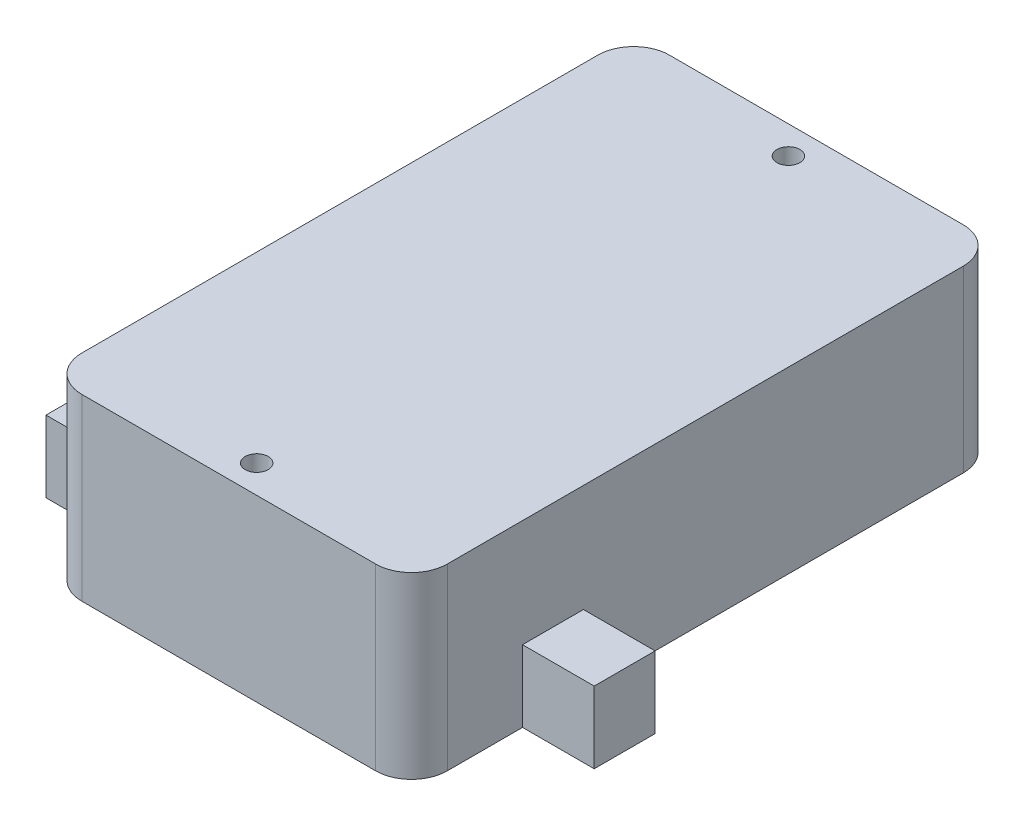
SolidWorks part; units mm, degrees
ref_plane "Front Plane" through (0, 0, 0) normal (0, 0, 1) x (1, 0, 0)
ref_plane "Top Plane" through (0, 0, 0) normal (0, 1, 0) x (1, 0, 0)
ref_plane "Right Plane" through (0, 0, 0) normal (1, 0, 0) x (0, 0, -1)
sketch "Sketch1" plane through (0, 0, 0) normal (0, 1, 0) x (1, 0, 0)
  line L0 (-25.5, 0) -> (25.5, 0) construction
  line L1 (-25.5, -41) -> (25.5, -41)
  line L2 (-25.5, -41) -> (-25.5, 41)
  line L3 (-25.5, 41) -> (25.5, 41)
  line L4 (25.5, -41) -> (25.5, 41)
  line L5 (-25.5, -41) -> (25.5, 41) construction
  line L6 (-25.5, 41) -> (25.5, -41) construction
  line L7 (11.5, -41) -> (11.5, -56) construction
  line L8 (25.5, -25.5) -> (35.5, -25.5)
  line L9 (25.5, -25.5) -> (25.5, -17)
  line L10 (25.5, -17) -> (35.5, -17)
  line L11 (35.5, -25.5) -> (35.5, -17)
  line L12 (25.5, -25.5) -> (35.5, -17) construction
  line L13 (25.5, -17) -> (35.5, -25.5) construction
  line L14 (-25.5, -5) -> (-35.5, -5)
  line L15 (-25.5, -5) -> (-25.5, -31)
  line L16 (-25.5, -31) -> (-35.5, -31)
  line L17 (-35.5, -5) -> (-35.5, -31)
  circle A0 centre (0, -37.1) radius 1.6
  circle A1 centre (0, 37.1) radius 1.6
  point P0 (0, 0)
  point P12 (30.5, -21.25)
  dimension "D3" = 3.2
  dimension "D1" = 51
  dimension "D2" = 82
  dimension "D4" = 3.9
  dimension "D5" = 8.5
  dimension "D6" = 24
  dimension "D7" = 10
  dimension "D8" = 26
  dimension "D9" = 36
  dimension "D10" = 10
  dimension "D11" = 14
  dimension "D12" = 15
extrude "Boss-Extrude1" add sketch "Sketch1" along normal blind 25 contours L1 L4 L3 L2 A0 A1 region at (0, 0, 0)
extrude "Boss-Extrude2" add sketch "Sketch1<3>" along normal blind 10 contours L8 L11 L10 L4 | L14 L17 L16 L2 region at (-30.5, 0, 18) region at (30.5, 0, 21.25)
sketch "Sketch1<3>" plane through (0, 0, 0) normal (0, 1, 0) x (1, 0, 0) same geometry as "Sketch1"
fillet "Fillet1" radius 5 4 edges at (-25.5, 12.5, -41) (25.5, 12.5, -41) (25.5, 12.5, 41) (-25.5, 12.5, 41)
equation "\"D4@Sketch1\"=2.2+1.7"
